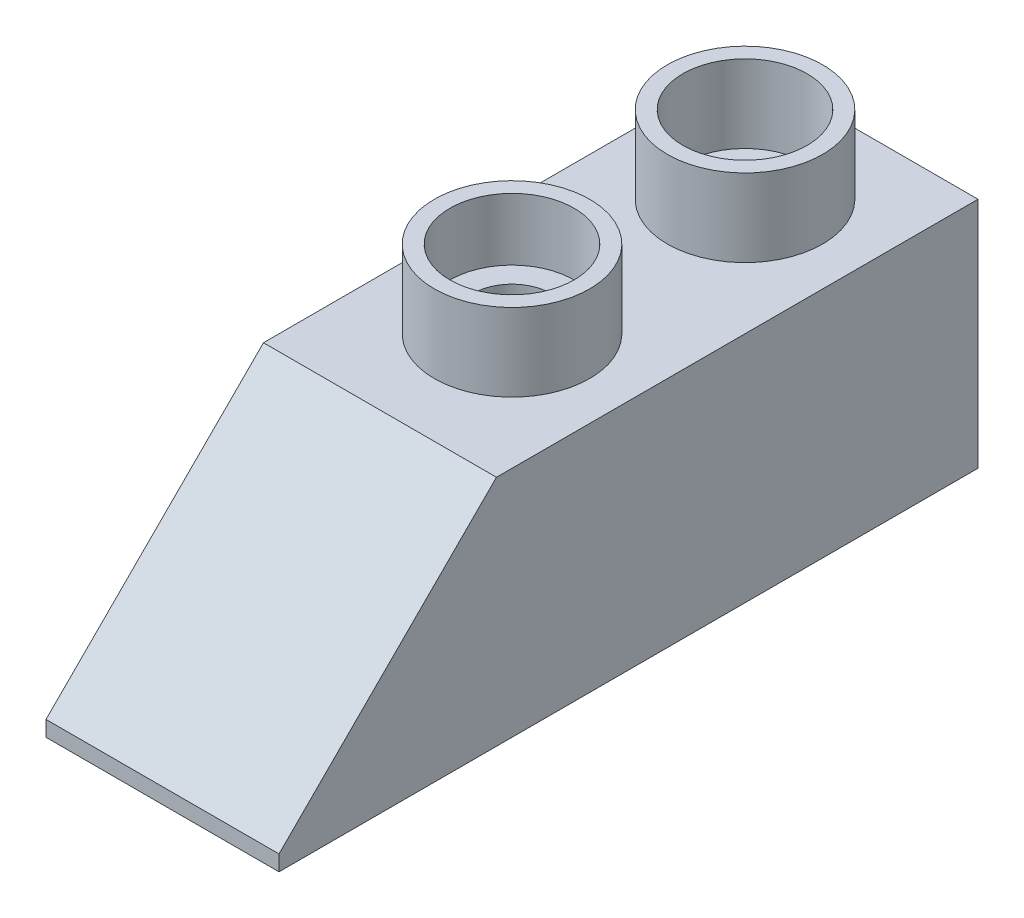
SolidWorks part; units mm, degrees
material "ABS"
ref_plane "Front Plane" through (0, 0, 0) normal (0, 0, 1) x (1, 0, 0)
ref_plane "Top Plane" through (0, 0, 0) normal (0, 1, 0) x (1, 0, 0)
ref_plane "Right Plane" through (0, 0, 0) normal (1, 0, 0) x (0, 0, -1)
sketch "Sketch1" plane through (0, 0, 0) normal (0, 1, 0) x (1, 0, 0)
  line L1 (0, 0) -> (-30, 0)
  line L2 (0, 0) -> (0, -90)
  line L3 (0, -90) -> (-30, -90)
  line L4 (-30, 0) -> (-30, -90)
  dimension "D1" = 30
  dimension "D2" = 90
extrude "Boss-Extrude1" add sketch "Sketch1" along normal blind 30 contours L4 L3 L2 L1
sketch "Sketch2" plane through (0, 30, 0) normal (0, 1, 0) x (1, 0, 0)
  line L0 (0, 0) -> (-30, 0) construction
  line L2 (-30, 0) -> (-30, -90) construction
  line L3 (0, 0) -> (0, -90) construction
  circle A0 centre (-15, -15) radius 10
  circle A1 centre (-15, -45) radius 10
  dimension "D1" = 20
  dimension "D3" = 15
  dimension "D4" = 20
  dimension "D2" = 15
  dimension "D5" = 30
  dimension "D6" = 15
extrude "Boss-Extrude5" add sketch "Sketch2" along normal blind 10 contours A1 | A0
sketch "Sketch5" plane through (0, 40, 0) normal (0, 1, 0) x (1, 0, 0)
  circle A0 centre (-15, -15) radius 8
  dimension "D1" = 16
extrude "Cut-Extrude1" cut sketch "Sketch5" against normal blind 10
sketch "Sketch8" plane through (0, 30, 0) normal (0, 1, 0) x (1, 0, 0)
  circle A0 centre (-15, -15) radius 5
  dimension "D1" = 10
extrude "Cut-Extrude3" cut sketch "Sketch8" against normal through all
hole_wizard "CBORE for M5 Hex Head Bolt1" positions "Sketch10" profile "Sketch11" counterbore size "M5" standard "ANSI Metric" end condition through all
sketch "Sketch10" plane through (0, 40, 0) normal (0, 1, 0) x (1, 0, 0)
  point P0 (-15, -45)
sketch "Sketch11" plane through (-15, 40, 45) normal (1, 0, 0) x (0, 0, 1)
  line L0 (0, 0) -> (0, 40)
  line L1 (0, 40) -> (5, 40)
  line L3 (5, 40) -> (5, 8)
  line L4 (5, 8) -> (8, 8)
  line L5 (8, 8) -> (8, 0)
  line L7 (8, 0) -> (0, 0)
  line L11 (0, -6.35) -> (0, 107.95) construction
  dimension "Thru Hole Dia." = 10
  dimension "Thru Hole Depth" = 40
  dimension "C'Bore Dia." = 16
  dimension "C'Bore Depth" = 8
chamfer "Chamfer2" distance 28 angle 45 1 edges at (-15, 30, 90)
shell "Shell2" thickness 3 removed face at (-15, 0, 50)
fillet "Fillet1" radius 0.5 19 edges at (-15, 0, 87) (-15, 0, 3) (-27, 13.5, 3) (-27, 0, 45) (-27, 0.3787, 87) (-15, 0, 23) (-15, 0, 53) (-3, 0.3787, 87) (-3, 0, 45) (-3, 13.5, 3) (-15, 27, 23) (-3, 27, 31.8787) (-15, 27, 3) (-27, 27, 31.8787) (-15, 27, 53) (-15, 27, 60.7574) (-27, 13.8787, 73.8787) (-15, 0.7574, 87) (-3, 13.8787, 73.8787)
